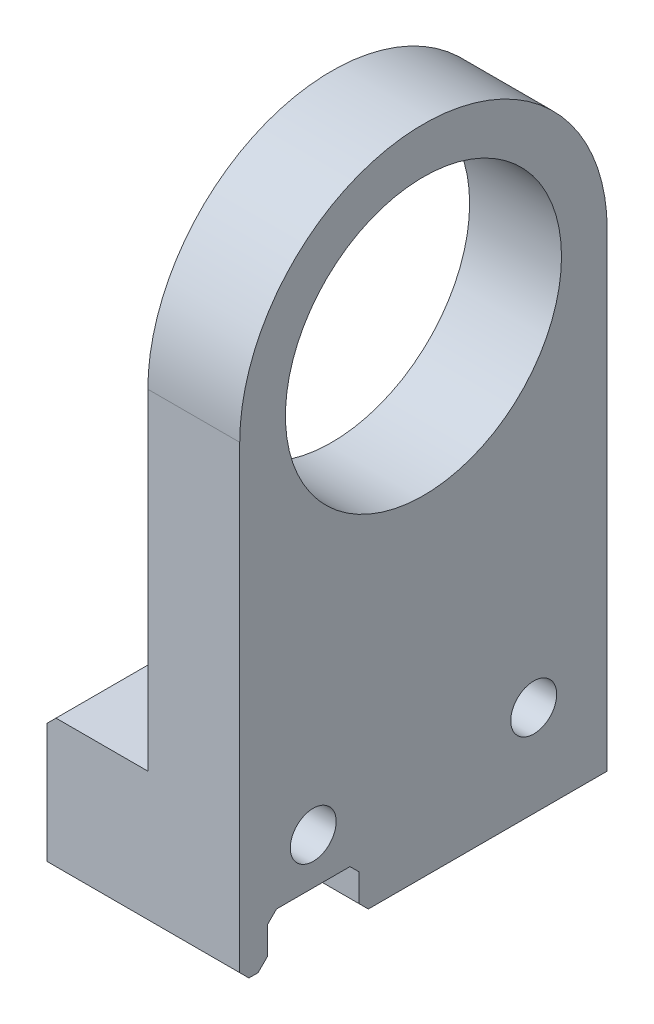
SolidWorks part; units mm, degrees
ref_plane "前视基准面" through (0, 0, 0) normal (0, 0, 1) x (1, 0, 0)
ref_plane "上视基准面" through (0, 0, 0) normal (0, 1, 0) x (1, 0, 0)
ref_plane "右视基准面" through (0, 0, 0) normal (1, 0, 0) x (0, 0, -1)
other "Configuration Table"
sketch "草图1" plane through (0, 0, 0) normal (0, 1, 0) x (1, 0, 0)
  line L1 (-10.5, -20) -> (10.5, -20)
  line L2 (-10.5, -20) -> (-10.5, 20)
  line L3 (-10.5, 20) -> (10.5, 20)
  line L4 (10.5, -20) -> (10.5, 20)
  line L5 (-10.5, -20) -> (10.5, 20) construction
  line L6 (-10.5, 20) -> (10.5, -20) construction
  point P0 (0, 0)
  dimension "D1" = 21
  dimension "D2" = 40
extrude "凸台-拉伸1" add sketch "草图1" along normal blind 5
sketch "草图2" plane through (0, 5, 0) normal (0, 1, 0) x (1, 0, 0)
  line L0 (-10.5, -20) -> (10.5, -20) construction
  line L1 (10.5, 20) -> (0.5, 20)
  line L2 (10.5, 20) -> (10.5, -20)
  line L3 (10.5, -20) -> (0.5, -20)
  line L4 (0.5, 20) -> (0.5, -20)
  dimension "D1" = 10
extrude "凸台-拉伸2" add sketch "草图2" along normal blind 36
sketch "草图3" plane through (10.5, 0, 0) normal (1, 0, 0) x (0, 0, -1)
  line L0 (-20, 41) -> (20, 41) construction
  circle A0 centre (0, 41) radius 20
extrude "凸台-拉伸3" add sketch "草图3" against normal blind 10
sketch "草图4" plane through (10.5, 0, 0) normal (1, 0, 0) x (0, 0, -1)
  circle A0 centre (0, 41) radius 15.025
  dimension "D1" = 30.05
extrude "切除-拉伸1" cut sketch "草图4" against normal blind 10
sketch "草图5" plane through (0, 0, 0) normal (0, -1, 0) x (1, 0, 0)
  line L0 (-10.5, -20) -> (-10.5, 20) construction
  circle A0 centre (-5.5, 0) radius 3.1
  dimension "D2" = 6.2
  dimension "D1" = 5
sketch "草图6" plane through (0, 0, 0) normal (0, -1, 0) x (1, 0, 0)
  line L1 (-10.5, 20) -> (10.5, 20)
  line L2 (-10.5, 20) -> (-10.5, -20)
  line L3 (-10.5, -20) -> (10.5, -20)
  line L4 (10.5, 20) -> (10.5, -20)
extrude "凸台-拉伸4" add sketch "草图6" along normal blind 10
extrude "切除-拉伸2" cut sketch "草图5" against normal mid plane 30
chamfer "倒角2" distance 1 angle 45 1 edges at (-5.5, -10, -3.1)
thread "螺纹线1" pitch 1 method extrude trim with end face yes profile "螺纹线轮廓1" start angle 0, offset 0, length 15, pitch 1, diameter 6.2
ref_plane "基准面1" through (-2.4, -9, 0) normal (0, 0, 1) x (1, 0, 0)
sketch "螺纹线轮廓1" plane through (-2.4, -9, 0) normal (0, 0, 1) x (1, 0, 0)
  line L0 (0, 0) -> (0, 1) construction
  line L11 (0, 0) -> (0, 0.875)
  line L12 (0, 0.875) -> (-0.5413, 0.5625)
  line L13 (-0.5413, 0.5625) -> (-0.5413, 0.3125)
  line L15 (-0.5413, 0.3125) -> (0, 0)
  line L17 (-0.5413, 0.4375) -> (0, 0.4375) construction
  point P2 (0, 0)
  dimension "Pitch" = 1
  dimension "Profile_Angle" = 60
  dimension "Profile_Land" = 0.25
  dimension "Profile_Height" = 0.5413
sketch "草图11" plane through (10.5, 0, 0) normal (1, 0, 0) x (0, 0, -1)
  line L0 (20, -10) -> (-20, -10) construction
  line L1 (-17, -10) -> (-7, -10)
  line L2 (-17, -10) -> (-17, -5)
  line L3 (-17, -5) -> (-7, -5)
  line L4 (-7, -10) -> (-7, -5)
  line L5 (-20, 41) -> (-20, -10) construction
  dimension "D1" = 10
  dimension "D2" = 5
  dimension "D3" = 3
extrude "切除-拉伸4" cut sketch "草图11" against normal blind 30
chamfer "倒角3" distance 1 angle 45 6 edges at (-10.5, 5, 0) (0, -10, 20) (0, -10, 17) (0, -5, 17) (0, -5, 7) (0, -10, 7)
sketch "草图12" plane through (10.5, 0, 0) normal (1, 0, 0) x (0, 0, -1)
  line L0 (0, 0) -> (20, 0) construction
  line L1 (20, 41) -> (20, -10) construction
  line L2 (0, 0) -> (-20, 0) construction
  line L3 (-20, 41) -> (-20, -9) construction
  circle A0 centre (12, 0) radius 2.5
  circle A1 centre (-12, 0) radius 2.5
  dimension "D2" = 5
  dimension "D4" = 5
  dimension "D1" = 8
  dimension "D3" = 8
extrude "切除-拉伸5" cut sketch "草图12" against normal blind 10
sketch "草图13" plane through (10.5, 0, 0) normal (1, 0, 0) x (0, 0, -1)
  line L0 (-15.025, 41) -> (15.025, 41) construction
  circle A0 centre (0, 41) radius 15.025 construction
